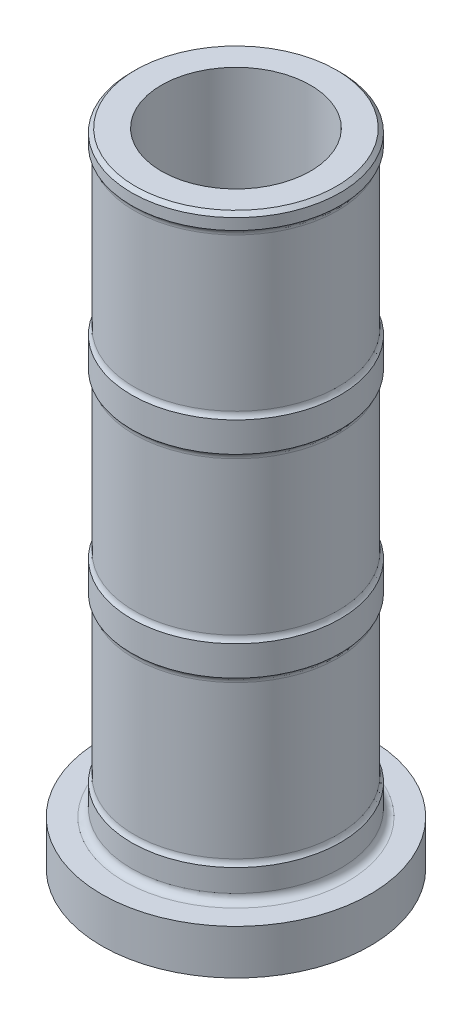
SolidWorks part; units mm, degrees
other "Markup1"
sketch "Sketch9" plane through (-9, 42.75, -9) normal (-0.8503, 0.5205, -0.078) x (0.4528, 0.7991, 0.3954)
other "Markup2"
sketch "Sketch10" plane through (-9, 42.75, -9) normal (-0.8503, 0.5205, -0.078) x (0.4528, 0.7991, 0.3954)
other "Markup3"
sketch "Sketch11" plane through (-9, 42.75, -9) normal (-0.8503, 0.5205, -0.078) x (0.4528, 0.7991, 0.3954)
ref_plane "Front Plane" through (0, 0, 0) normal (0, 0, 1) x (1, 0, 0)
ref_plane "Top Plane" through (0, 0, 0) normal (0, 1, 0) x (1, 0, 0)
ref_plane "Right Plane" through (0, 0, 0) normal (1, 0, 0) x (0, 0, -1)
sketch "Sketch1" plane through (0, 0, 0) normal (0, 1, 0) x (1, 0, 0)
  circle A1 centre (0, 0) radius 9
  dimension "D1" = 18
extrude "Boss-Extrude1" add sketch "Sketch1" along normal blind 3
sketch "Sketch2" plane through (0, 3, 0) normal (0, 1, 0) x (1, 0, 0)
  circle A0 centre (0, 0) radius 7
  dimension "D1" = 14
extrude "Boss-Extrude2" add sketch "Sketch2" along normal blind 2
sketch "Sketch3" plane through (0, 5, 0) normal (0, 1, 0) x (1, 0, 0)
  circle A0 centre (0, 0) radius 6.825
  dimension "D1" = 13.65
extrude "Boss-Extrude3" add sketch "Sketch3" along normal blind 11
sketch "Sketch4" plane through (0, 16, 0) normal (0, 1, 0) x (1, 0, 0)
  circle A0 centre (0, 0) radius 7
  dimension "D1" = 14
extrude "Boss-Extrude4" add sketch "Sketch4" along normal blind 2
sketch "Sketch5" plane through (0, 18, 0) normal (0, 1, 0) x (1, 0, 0)
  circle A0 centre (0, 0) radius 6.825
  dimension "D1" = 13.65
extrude "Boss-Extrude5" add sketch "Sketch5" along normal blind 11
sketch "Sketch6" plane through (0, 29, 0) normal (0, 1, 0) x (1, 0, 0)
  circle A0 centre (0, 0) radius 7
extrude "Boss-Extrude6" add sketch "Sketch6" along normal blind 2
sketch "Sketch7" plane through (0, 31, 0) normal (0, 1, 0) x (1, 0, 0)
  circle A0 centre (0, 0) radius 6.825
  dimension "D1" = 13.65
extrude "Boss-Extrude7" add sketch "Sketch7" along normal blind 11
sketch "Sketch8" plane through (0, 42, 0) normal (0, 1, 0) x (1, 0, 0)
  circle A0 centre (0, 0) radius 7
extrude "Boss-Extrude8" add sketch "Sketch8" along normal blind 1
fillet "Fillet3" radius 0.5 7 edges at (0, 3, 7) (0, 5, 6.825) (0, 42, 6.825) (0, 31, 6.825) (0, 29, 6.825) (0, 18, 6.825) (0, 16, 6.825)
chamfer "Chamfer2" distance 0.25 1 edges at (0, 43, 7)
sketch "Sketch13" plane through (0, 43, 0) normal (0, 1, 0) x (1, 0, 0)
  circle A0 centre (0, 0) radius 5
  dimension "D1" = 10
extrude "Cut-Extrude1" cut sketch "Sketch13" against normal blind 15
sketch "Sketch14" plane through (0, 28, 0) normal (0, 1, 0) x (1, 0, 0)
  circle A0 centre (0, 0) radius 4
  dimension "D1" = 8
extrude "Cut-Extrude2" cut sketch "Sketch14" against normal up to surface (28 mm away) up to face at (0, 0, 9)
fillet "Fillet4" radius 1 1 edges at (0, 28, 5)
